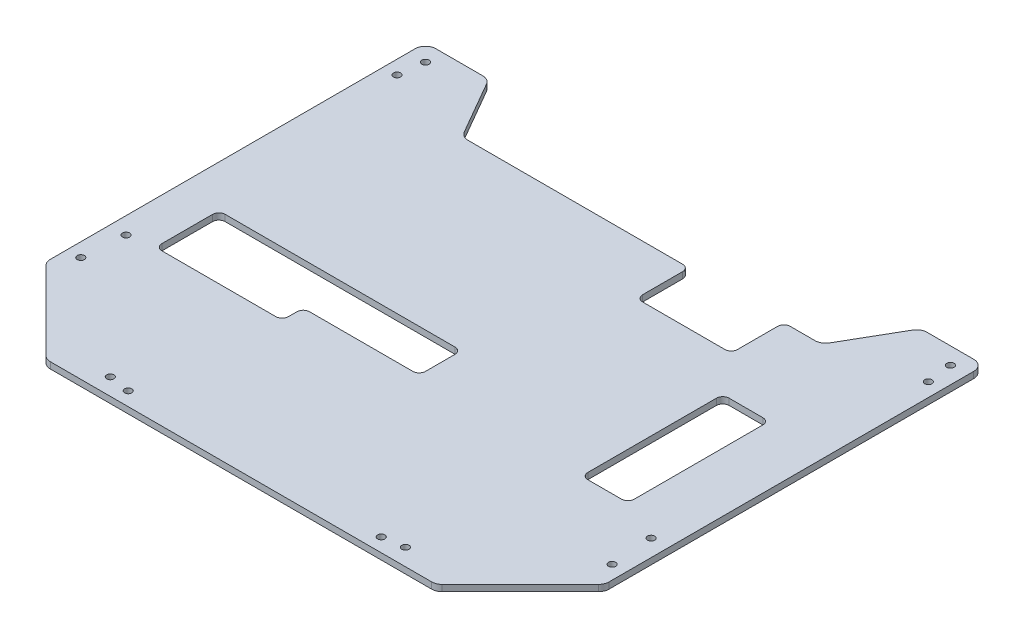
SolidWorks part; units mm, degrees
material "Acier non allié"
ref_plane "Front" through (0, 0, 0) normal (0, 0, 1) x (1, 0, 0)
ref_plane "Top" through (0, 0, 0) normal (0, 1, 0) x (1, 0, 0)
ref_plane "Right" through (0, 0, 0) normal (1, 0, 0) x (0, 0, -1)
sketch "Esquisse1" plane through (0, 0, 0) normal (0, 1, 0) x (1, 0, 0)
  line L0 (0, 0) -> (0, 1919.0564) construction
  line L1 (-92.5, 0) -> (92.5, 0)
  line L2 (92.5, 0) -> (132.5, 40)
  line L3 (132.5, 40) -> (132.5, 220)
  line L4 (132.5, 220) -> (102.5, 220)
  line L5 (102.5, 220) -> (85.1795, 190)
  line L6 (85.1795, 190) -> (-85.1795, 190)
  line L7 (-102.5, 220) -> (-85.1795, 190)
  line L8 (-132.5, 220) -> (-102.5, 220)
  line L9 (-132.5, 40) -> (-132.5, 220)
  line L10 (-92.5, 0) -> (-132.5, 40)
  point P12 (0, 190)
  dimension "D1" = 132.5
  dimension "D2" = 220
  dimension "D3" = 30
  dimension "D4" = 30
  dimension "D5" = 40
  dimension "D6" = 40
  dimension "D7" = 60
extrude "Boss.-Extru.1" add sketch "Esquisse1" along normal blind 3
fillet "Congé1" radius 5 10 edges at (132.5, 1.5, -220) (102.5, 1.5, -220) (85.1795, 1.5, -190) (-85.1795, 1.5, -190) (-102.5, 1.5, -220) (-132.5, 1.5, -220) (-132.5, 1.5, -40) (-92.5, 1.5, 0) (92.5, 1.5, 0) (132.5, 1.5, -40)
sketch "Esquisse2" plane through (0, 0, 0) normal (0, -1, 0) x (1, 0, 0)
  line L0 (0, 0) -> (0, -330.9968) construction
  line L1 (-90.4289, 0) -> (90.4289, 0) construction
  line L2 (-105.3868, -220) -> (-127.5, -220) construction
  line L3 (-132.5, -215) -> (-132.5, -42.0711) construction
  line L4 (-90.4289, 0) -> (90.4289, 0) construction
  line L5 (132.5, -42.0711) -> (132.5, -215) construction
  circle A0 centre (-70, -8) radius 1
  circle A1 centre (-124.5, -70) radius 1
  circle A2 centre (-124.5, -212) radius 1
  circle A3 centre (124.5, -212) radius 1
  circle A4 centre (124.5, -70) radius 1
  circle A5 centre (70, -8) radius 1
  circle A6 centre (126, -50) radius 1.5
  circle A7 centre (126, -200) radius 1.5
  circle A8 centre (-60, -6.5) radius 1.5
  circle A9 centre (60, -6.5) radius 1.5
  circle A10 centre (-126, -50) radius 1.5
  circle A11 centre (-126, -200) radius 1.5
  dimension "D3" = 2
  dimension "D6" = 2
  dimension "D9" = 2
  dimension "D12" = 3
  dimension "D15" = 3
  dimension "D16" = 3
  dimension "D17" = 3
  dimension "D24" = 3
  dimension "D27" = 3
  dimension "D1" = 70
  dimension "D2" = 8
  dimension "D4" = 124.5
  dimension "D5" = 70
  dimension "D7" = 8
  dimension "D8" = 8
  dimension "D10" = 50
  dimension "D11" = 6.5
  dimension "D13" = 15
  dimension "D14" = 6.5
  dimension "D18" = 10
  dimension "D19" = 6.5
  dimension "D20" = 6.5
  dimension "D21" = 10
  dimension "D22" = 50
  dimension "D23" = 6.5
  dimension "D25" = 15
  dimension "D26" = 6.5
extrude "Enlèv. mat.-Extru.1" cut sketch "Esquisse2" against normal through all
hole_wizard "Dégagement M31" positions "Esquisse3" profile "Esquisse4" hole size "M3" standard "ISO" end condition through all
sketch "Esquisse3" plane through (0, 0, 0) normal (0, -1, 0) x (-1, 0, 0)
  point P0 (-70, 8)
  point P3 (-124.5, 70)
  point P6 (-124.5, 212)
  point P9 (124.5, 212)
  point P12 (124.5, 70)
  point P15 (70, 8)
  point P18 (-126, 200)
  point P21 (-126, 50)
  point P24 (-60, 6.5)
  point P27 (60, 6.5)
  point P44 (126, 50)
  point P49 (126, 200)
sketch "Esquisse4" plane through (70, 0, -8) normal (1, 0, 0) x (0, 0, -1)
  line L0 (0, 0) -> (0, 3)
  line L1 (0, 3) -> (1.7, 3)
  line L2 (1.7, 3) -> (1.7, 0)
  line L5 (1.7, 0) -> (0, 0)
  line L11 (0, -6.35) -> (0, 107.95) construction
  dimension "Diamètre du perçage jusqu'au prochain" = 3.4
  dimension "Profondeur du perçage jusqu'au prochain" = 3
sketch "Esquisse5" plane through (0, 0, 0) normal (0, -1, 0) x (1, 0, 0)
  line L6 (82.2927, -190) -> (-82.2927, -190) construction
  line L7 (22.5, -190) -> (67.5, -190)
  line L20 (22.5, -190) -> (22.5, -165)
  line L21 (22.5, -165) -> (67.5, -165)
  line L22 (67.5, -190) -> (67.5, -165)
  line L23 (132.5, -42.0711) -> (132.5, -215) construction
  line L24 (-112.5, -82) -> (-112.5, -72)
  line L25 (-112.5, -102) -> (2.5, -102)
  line L26 (-112.5, -102) -> (-112.5, -82)
  line L27 (-52.5, -82) -> (2.5, -82)
  line L28 (2.5, -102) -> (2.5, -82)
  line L29 (-132.5, -215) -> (-132.5, -42.0711) construction
  line L30 (127.5, -220) -> (105.3868, -220) construction
  line L31 (82.5, -146) -> (104.5, -146)
  line L32 (82.5, -146) -> (82.5, -79)
  line L33 (82.5, -79) -> (104.5, -79)
  line L34 (104.5, -146) -> (104.5, -79)
  line L35 (-90.4289, 0) -> (90.4289, 0) construction
  line L36 (-112.5, -72) -> (-52.5, -72)
  line L37 (-52.5, -82) -> (-52.5, -72)
  dimension "D1" = 65
  dimension "D2" = 110
  dimension "D3" = 25
  dimension "D4" = 82
  dimension "D5" = 135
  dimension "D6" = 20
  dimension "D7" = 115
  dimension "D8" = 50
  dimension "D9" = 74
  dimension "D10" = 67
  dimension "D11" = 22
  dimension "D15" = 30
  dimension "D16" = 60
extrude "Enlèv. mat.-Extru.2" cut sketch "Esquisse5" against normal through all
fillet "Congé2" radius 3 14 edges at (67.5, 1.5, -190) (67.5, 1.5, -165) (22.5, 1.5, -165) (22.5, 1.5, -190) (104.5, 1.5, -146) (82.5, 1.5, -146) (82.5, 1.5, -79) (104.5, 1.5, -79) (2.5, 1.5, -82) (2.5, 1.5, -102) (-112.5, 1.5, -102) (-52.5, 1.5, -72) (-52.5, 1.5, -82) (-112.5, 1.5, -72)
equation "\"WIDTH\"= 300mm'Total width of the robot"
equation "\"LENGTH\"= 220mm'Total length of the robot"
equation "\"CUT_DEPTH\"= 45mm'Depth of the cut on the edges of the plate"
equation "\"Plate_th\"= 3mm'Thickness of the plate"
equation "\"D1\"= \"Plate_th\""
